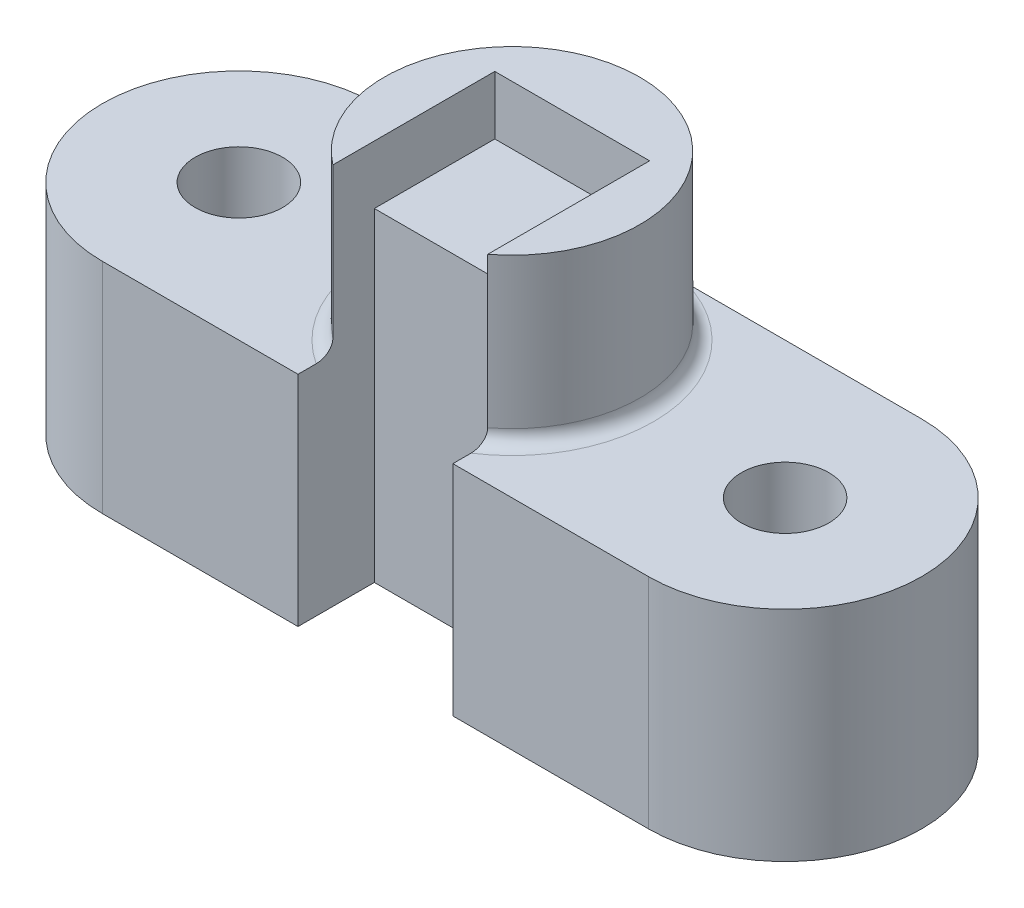
SolidWorks part; units mm, degrees
ref_plane "Front Plane" through (0, 0, 0) normal (0, 0, 1) x (1, 0, 0)
ref_plane "Top Plane" through (0, 0, 0) normal (0, 1, 0) x (1, 0, 0)
ref_plane "Right Plane" through (0, 0, 0) normal (1, 0, 0) x (0, 0, -1)
sketch "Sketch2" plane through (0, 0, 0) normal (0, 1, 0) x (1, 0, 0)
  line L0 (-7.9375, 0) -> (7.9375, 0) construction
  line L1 (-7.9375, 3.9688) -> (7.9375, 3.9688)
  line L2 (-7.9375, -3.9688) -> (7.9375, -3.9687)
  arc A0 (-7.9375, 3.9688) -> (-7.9375, -3.9688) centre (-7.9375, 0) ccw
  arc A2 (7.9375, -3.9687) -> (7.9375, 3.9688) centre (7.9375, 0) ccw
  circle A3 centre (-7.9375, 0) radius 1.27
  circle A4 centre (7.9375, 0) radius 1.27
  point P2 (0, 0)
  dimension "D1" = 15.875
  dimension "D3" = 2.54
  dimension "D2" = 7.9375
extrude "Boss-Extrude1" add sketch "Sketch2" against normal blind 6.35
sketch "Sketch3" plane through (0, 0, 0) normal (0, 1, 0) x (1, 0, 0)
  line L1 (0, -3.7147) -> (0, -3.9687) construction
  line L2 (-7.9375, -3.9688) -> (7.9375, -3.9687) construction
  circle A0 centre (0, 0) radius 3.7147
  dimension "D1" = 0.254
extrude "Boss-Extrude2" add sketch "Sketch3" along normal blind 4.7625
fillet "Fillet1" radius 0.3969 1 edges at (0, 0, 3.7147)
sketch "Sketch4" plane through (0, 4.7625, 0) normal (0, 1, 0) x (1, 0, 0)
  line L1 (-2.25, -1.75) -> (2.25, -1.75)
  line L2 (-2.25, -1.75) -> (-2.25, 1.75)
  line L3 (-2.25, 1.75) -> (2.25, 1.75)
  line L4 (2.25, -1.75) -> (2.25, 1.75)
  line L5 (-2.25, -1.75) -> (2.25, 1.75) construction
  line L6 (-2.25, 1.75) -> (2.25, -1.75) construction
  point P0 (0, 0)
  dimension "D1" = 3.5
  dimension "D2" = 4.5
extrude "Cut-Extrude1" cut sketch "Sketch4" against normal blind 1.7
sketch "Sketch5" plane through (0, 0, 1.75) normal (0, 0, -1) x (-1, 0, 0)
  line L0 (-9.2075, -6.35) -> (-6.6675, -6.35) construction
  line L1 (2.25, 4.7625) -> (-2.25, 4.7625)
  line L2 (2.25, 4.7625) -> (2.25, -6.35)
  line L3 (2.25, -6.35) -> (-2.25, -6.35)
  line L4 (-2.25, 4.7625) -> (-2.25, -6.35)
extrude "Cut-Extrude2" cut sketch "Sketch5" against normal through all
fillet "Fillet2" [suppressed] radius 0.3969
